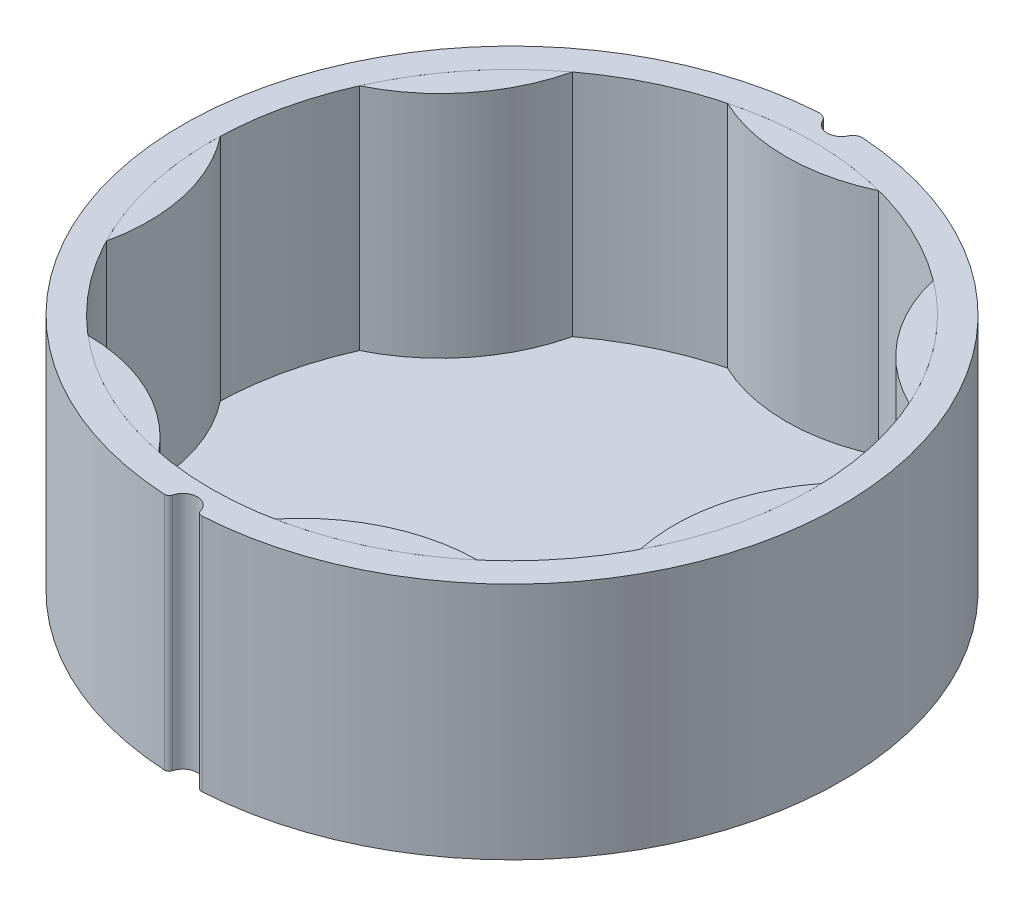
SolidWorks part; units mm, degrees
ref_plane "Front Plane" through (0, 0, 0) normal (0, 0, 1) x (1, 0, 0)
ref_plane "Top Plane" through (0, 0, 0) normal (0, 1, 0) x (1, 0, 0)
ref_plane "Right Plane" through (0, 0, 0) normal (1, 0, 0) x (0, 0, -1)
sketch "Sketch1" plane through (0, 0, 0) normal (0, 1, 0) x (1, 0, 0)
  line L3 (0, 0.002) -> (0, 3.7877) construction
  line L4 (0, 3.7877) -> (2.417, 3.7877)
  line L5 (0, 3.7877) -> (-2.417, 3.7877)
  arc A0 (1.9642, -34.442) -> (34.1982, 4.5552) centre (0, 0.002) ccw
  arc A2 (-2.417, 3.7877) -> (2.417, 3.7877) centre (0, 0.002) ccw
  circle A3 centre (0, 0.002) radius 34.5 construction
  arc A7 (-1.3541, 33.8562) -> (1.3541, 33.8562) centre (0, 34.5015) ccw
  arc A8 (34.1982, 4.5552) -> (2.3241, 34.4236) centre (0, 0.002) ccw
  arc A9 (-2.3241, 34.4236) -> (-34.1982, 4.5552) centre (0, 0.002) ccw
  arc A10 (-34.1982, 4.5552) -> (-1.9642, -34.442) centre (0, 0.002) ccw
  arc A11 (1.3541, 33.8562) -> (2.3241, 34.4236) centre (2.2568, 33.4259) cw
  arc A12 (-1.3541, 33.8562) -> (-2.3241, 34.4236) centre (-2.2568, 33.4259) ccw
  arc A13 (1.4518, -34.0686) -> (-1.4518, -34.0686) centre (0, -34.4457) ccw
  arc A14 (1.4518, -34.0686) -> (1.9642, -34.442) centre (1.9358, -33.9428) ccw
  arc A15 (-1.4518, -34.0686) -> (-1.9642, -34.442) centre (-1.9358, -33.9428) cw
  point P15 (1.4997, 34.4694)
  dimension "D2" = 4.834
  dimension "D3" = 4.4915
  dimension "D4" = 34.5
  dimension "D5" = 1
  dimension "D6" = 1.5
  dimension "D7" = 0.5
  dimension "D11" = 1.4997
sketch "Sketch2" plane through (0, 0, 0) normal (0, 1, 0) x (1, 0, 0)
  line L0 (0, 31.5) -> (0, 28.7) construction
  line L1 (-7.9352, 30.4841) -> (0, 31.5) construction
  line L2 (0, 31.5) -> (7.9352, 30.4841) construction
  circle A16 centre (0, 0) radius 31.5
  arc A17 (-7.9352, 30.4841) -> (7.9352, 30.4841) centre (0, 47.2388) ccw
  dimension "D1" = 63
  dimension "D2" = 8
  dimension "D3" = 2.8
extrude "Boss-Extrude1" add sketch "Sketch1" along normal blind 25 contours A10 A0 A8 A7 A9 A2 L5 L4 | L5 A2 L4 region at (0, 0, 0.1522) region at (2.2155, 0, 33.5591)
extrude "Cut-Extrude2" cut sketch "Sketch2" along normal up to next from offset 1 contours A17 A16 | A16 region at (0, 0, 0.2917)
extrude "Boss-Extrude2" add sketch "Sketch2<2>" along normal up to surface (25 mm away) separate body contours A16 A17 region at (0, 0, -30.1734) up to face at (0, 25, 31.5)
sketch "Sketch2<2>" plane through (0, 0, 0) normal (0, 1, 0) x (1, 0, 0) same geometry as "Sketch2"
pattern_circular "CirPattern2" count 7 over 360 about axis through (0, 25, 0) along (0, 1, 0) of bodies 106
sketch "Sketch3" plane through (0, 25, 0) normal (0, 1, 0) x (1, 0, 0)
  line L0 (-28.781, 12.8025) -> (-30.7102, 7.0094) construction
  line L1 (-30.7102, 7.0094) -> (-31.4856, 0.9529) construction
  line L2 (28.781, 12.8025) -> (30.7102, 7.0094) construction
  line L3 (30.7102, 7.0094) -> (31.4856, 0.9529) construction
  line L4 (-6.0772, -30.9082) -> (0, -31.5) construction
  line L5 (0, -31.5) -> (6.0772, -30.9082) construction
  line L6 (-7.9352, 30.4841) -> (0, 28.7) construction
  line L7 (0, 28.7) -> (7.9352, 30.4841) construction
  line L8 (-28.781, 12.8025) -> (-22.4386, 17.8942) construction
  line L9 (-22.4386, 17.8942) -> (-18.8859, 25.2106) construction
  line L10 (18.8859, 25.2106) -> (22.4386, 17.8942) construction
  line L11 (22.4386, 17.8942) -> (28.781, 12.8025) construction
  line L12 (27.9804, -6.3864) -> (27.9541, -14.5196) construction
  circle A0 centre (0, 0) radius 31.5 construction
  arc A1 (-6.0772, -30.9082) -> (-20.376, -24.0223) centre (-20.4961, -42.5607) ccw construction
  arc A2 (-7.9352, 30.4841) -> (7.9352, 30.4841) centre (0, 47.2388) ccw construction
  arc A3 (-28.781, 12.8025) -> (-18.8859, 25.2106) centre (-36.9328, 29.4529) ccw construction
  arc A4 (18.8859, 25.2106) -> (28.781, 12.8025) centre (36.9328, 29.4529) ccw construction
  arc A5 (31.4856, 0.9529) -> (27.9541, -14.5196) centre (46.0544, -10.5116) ccw construction
